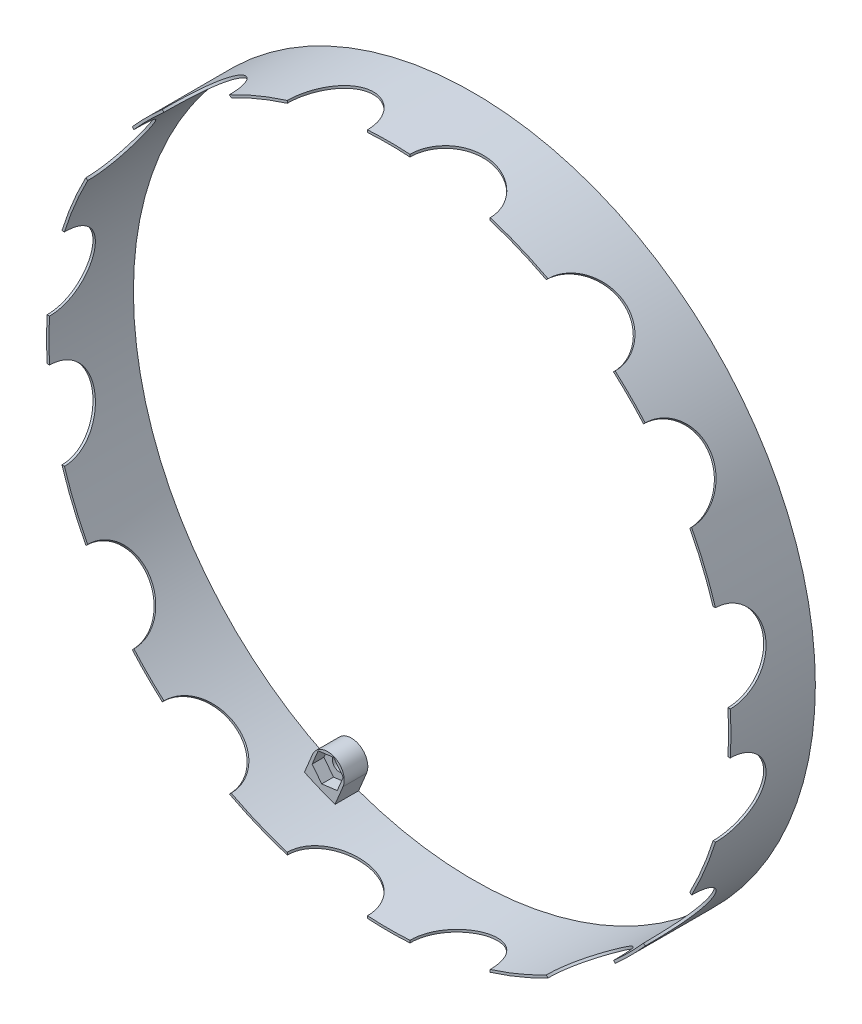
SolidWorks part; units mm, degrees
material "ABS"
ref_plane "Ebene vorne" through (0, 0, 0) normal (0, 0, 1) x (1, 0, 0)
ref_plane "Ebene oben" through (0, 0, 0) normal (0, 1, 0) x (1, 0, 0)
ref_plane "Ebene rechts" through (0, 0, 0) normal (1, 0, 0) x (0, 0, -1)
sketch "Skizze4" plane through (0, 0, 0) normal (0, 0, 1) x (1, 0, 0)
  circle A0 centre (0, 0) radius 72.5
  circle A1 centre (0, 0) radius 72
  dimension "D1" = 145
  dimension "D2" = 0.5
extrude "Base Ring" add sketch "Skizze4" along normal blind 17.9
sketch "Skizze5" plane through (0, 0, 0) normal (1, 0, 0) x (0, 0, -1)
  line L0 (0, 0) -> (-17.9, 0) construction
  line L1 (-17.9, 72.5) -> (-17.9, -72.5) construction
  line L2 (0, -72.5) -> (0, 72.5) construction
  line L3 (-17.9, 4.5) -> (-48.8483, 4.5)
  line L4 (-17.9, 4.5) -> (-17.9, 21.5) construction
  line L5 (-17.9, 21.5) -> (-48.8483, 21.5)
  line L6 (-48.8483, 4.5) -> (-48.8483, 21.5)
  line L7 (-17.9, 4.5) -> (-48.8483, 21.5) construction
  line L8 (-17.9, 21.5) -> (-48.8483, 4.5) construction
  line L9 (-48.8483, 13) -> (0, 13) construction
  line L10 (-17.9, -13) -> (0, -13) construction
  line L12 (-17.9, -21.5) -> (-48.8483, -21.5)
  line L13 (-17.9, -21.5) -> (-17.9, -4.5) construction
  line L14 (-17.9, -4.5) -> (-48.8483, -4.5)
  line L15 (-48.8483, -21.5) -> (-48.8483, -4.5)
  line L16 (-17.9, -21.5) -> (-48.8483, -4.5) construction
  line L17 (-17.9, -4.5) -> (-48.8483, -21.5) construction
  arc A0 (-17.9, 21.5) -> (-17.9, 4.5) centre (-17.9, 13) cw
  arc A1 (-17.9, -4.5) -> (-17.9, -21.5) centre (-17.9, -13) cw
  point P5 (-33.3742, 13)
  point P17 (-33.3742, -13)
  dimension "D1" = 17
  dimension "D3" = 26
  dimension "D2" = 17.9
extrude "Ultrasonic Cut" cut sketch "Skizze5" along normal through all
pattern_circular "Rotation I" count 8 over 360 about axis through (0, 0, 17.9) along (0, 0, -1) of "Ultrasonic Cut" reverse direction yes
sketch "Skizze6" plane through (0, 0, 0) normal (0, 0, 1) x (1, 0, 0)
  line L0 (0, 0) -> (72, 0) construction
  line L1 (0, 0) -> (28.5999, 69.0463) construction
  line L4 (30.7542, 65.1013) -> (24.2871, 67.7801) construction
  line L5 (24.2871, 67.7801) -> (22.5976, 63.7013)
  line L6 (22.5976, 63.7013) -> (29.0647, 61.0225)
  line L7 (29.0647, 61.0225) -> (30.7542, 65.1013)
  arc A2 (24.2871, 67.7801) -> (30.7542, 65.1013) centre (0, 0) cw
  arc A3 (33.386, 63.7916) -> (21.5, 68.715) centre (0, 0) ccw construction
  arc A4 (22.5976, 63.7013) -> (29.0647, 61.0225) centre (25.8311, 62.3619) ccw
  dimension "D1" = 7
  dimension "D2" = 67.5
  dimension "D3" = 67.5
extrude "Screw Base" add sketch "Skizze6" along normal blind 5 contours L6 A4 | A2 L5 L6 L7 region at (26.6868, 64.4276, 0) region at (25.2627, 60.9895, 0)
sketch "Skizze7" plane through (0, 0, 5) normal (0, 0, 1) x (1, 0, 0)
  line L1 (29.1225, 62.7952) -> (27.1016, 65.4289)
  line L2 (27.1016, 65.4289) -> (23.8102, 64.9956)
  line L3 (23.8102, 64.9956) -> (22.5398, 61.9286)
  line L4 (22.5398, 61.9286) -> (24.5607, 59.2948)
  line L5 (24.5607, 59.2948) -> (27.8521, 59.7281)
  line L6 (27.8521, 59.7281) -> (29.1225, 62.7952)
  line L7 (24.2871, 67.7801) -> (22.5976, 63.7013) construction
  circle A0 centre (25.8311, 62.3619) radius 1.5
  circle A1 centre (25.8311, 62.3619) radius 2.875 construction
  dimension "D1" = 3
  dimension "D2" = 5.75
extrude "Screw Center" cut sketch "Skizze7" against normal through all contours A0
extrude "Hex Nut" cut sketch "Skizze7<3>" against normal blind 2.5
sketch "Skizze7<3>" plane through (0, 0, 5) normal (0, 0, 1) x (1, 0, 0) same geometry as "Skizze7"
pattern_circular "Kreismuster2" count 2 over 360 about axis through (0, 0, 17.9) along (0, 0, -1) of "Screw Base", "Screw Center", "Hex Nut" reverse direction yes
equation "\"D_outer\"= 145mm"
equation "\"d_inner\"= 130mm"
equation "\"d_spacers\"= 135mm"
equation "\"d_spacer_hole\"= 3.5mm"
equation "\"D1@Skizze4\"=\"D_outer\""
